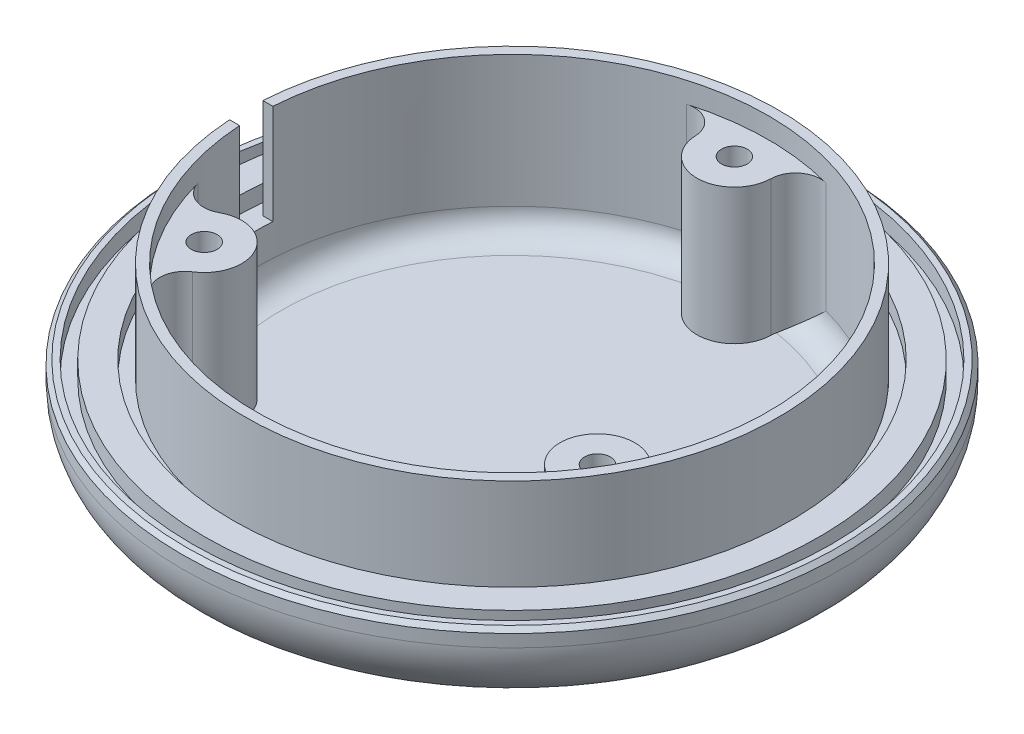
SolidWorks part; units mm, degrees
ref_plane "Plan de face" through (0, 0, 0) normal (0, 0, 1) x (1, 0, 0)
ref_plane "Plan de dessus" through (0, 0, 0) normal (0, 1, 0) x (1, 0, 0)
ref_plane "Plan de droite" through (0, 0, 0) normal (1, 0, 0) x (0, 0, -1)
sketch "Esquisse2" plane through (0, 0, 0) normal (0, 0, 1) x (1, 0, 0)
  line L0 (-39.6, 8) -> (-39.6, 10)
  line L1 (0, 0) -> (-32, 0)
  line L2 (-39.6, 10) -> (-38.4, 10)
  line L3 (-38.4, 10) -> (-38.4, 8)
  line L4 (0, 24.4124) -> (0, -18.1737) construction
  line L5 (0, 1.2) -> (-30.8, 1.2)
  line L7 (-32, 8) -> (-32, 20)
  line L8 (-32, 20) -> (-30.8, 20)
  line L9 (-30.8, 20) -> (-30.8, 1.2)
  line L10 (-32, 8) -> (-33.5, 8)
  line L11 (0, 0) -> (0, 1.2)
  line L12 (-38.4, 8) -> (-36.9, 8)
  line L13 (-36.9, 8) -> (-36.9, 10)
  line L17 (-36.9, 10) -> (-33.5, 10)
  line L18 (-33.5, 8) -> (-33.5, 10)
  arc A0 (-39.6, 8) -> (-32, 0) centre (-31.5895, 8) ccw
  circle A1 centre (-34.3, 4.5) radius 2.75
  point P12 (-39.6, 10)
  dimension "D2" = 32
  dimension "D5" = 12
  dimension "D20" = 5.5
  dimension "D4" = 1.5
  dimension "D6" = 30.8
  dimension "D7" = 2
  dimension "D8" = 3.4
  dimension "D9" = 90
  dimension "D10" = 2
  dimension "D11" = 1.2
  dimension "D12" = 2
  dimension "D13" = 1.2
  dimension "D14" = 8
  dimension "D17" = 1.5
  dimension "D18" = 1.2
  dimension "D19" = 8
  dimension "D21" = 3.5
  dimension "D22" = 4.5
revolve "Révolution1" add sketch "Esquisse2" angle 360 about L4
sketch "Esquisse3" plane through (0, 0, 0) normal (1, 0, 0) x (0, 0, -1)
  line L0 (-39.6, 8) -> (39.6, 8) construction
  line L1 (2, 21.9768) -> (-2, 21.9768)
  line L2 (2, 21.9768) -> (2, 8)
  line L3 (2, 8) -> (-2, 8)
  line L4 (-2, 21.9768) -> (-2, 8)
  dimension "D1" = 2
  dimension "D2" = 4
extrude "Enlèv. mat.-Extru.1" cut sketch "Esquisse3" against normal blind 32
sketch "Esquisse4" plane through (0, 1.2, 0) normal (0, 1, 0) x (1, 0, 0)
  line L0 (4.2215, 26.9986) -> (4.2215, 30.6492)
  line L1 (-4.7785, 26.9986) -> (-4.7785, 30.5673)
  line L2 (21.2707, -17.1552) -> (24.4323, -18.9805)
  line L3 (25.7707, -9.361) -> (28.8614, -11.1454)
  line L4 (-25.4922, -9.8434) -> (-28.6538, -11.6687)
  line L5 (-20.9922, -17.6376) -> (-24.0828, -19.422)
  arc A0 (4.2215, 30.6492) -> (-4.7785, 30.5673) centre (0, 0) ccw
  circle A1 centre (-0.2785, 26.9986) radius 1.55
  arc A2 (24.4323, -18.9805) -> (28.8614, -11.1454) centre (0, 0) ccw
  arc A3 (-4.7785, 26.9986) -> (4.2215, 26.9986) centre (-0.2785, 26.9986) ccw
  circle A4 centre (23.5207, -13.2581) radius 1.55
  arc A5 (25.7707, -9.361) -> (21.2707, -17.1552) centre (23.5207, -13.2581) ccw
  arc A6 (-28.6538, -11.6687) -> (-24.0828, -19.422) centre (0, 0) ccw
  circle A7 centre (-23.2422, -13.7405) radius 1.55
  arc A8 (-20.9922, -17.6376) -> (-25.4922, -9.8434) centre (-23.2422, -13.7405) ccw
  circle A13 centre (23.5207, -13.2581) radius 1.55 [skipped]
  circle A14 centre (-23.2422, -13.7405) radius 1.55 [skipped]
  point P8 (0, 0)
  point P9 (0, 0)
  point P10 (0, 0)
  point P11 (0, 0)
  point P12 (0, 0)
  point P13 (0, 0)
  point P16 (0, 0)
  point P21 (0, 0)
  point P33 (0, 0)
  point P34 (0, 0)
  point P35 (0, 0)
  point P37 (0, 0)
  point P41 (0, 0)
  dimension "D1" = 3.1
  dimension "D3" = 3
  dimension "D4" = 3
  dimension "D5" = 4.5
  dimension "D2" = 27
extrude "Boss.-Extru.1" add sketch "Esquisse4" along normal blind 16.3
fillet "Congé1" radius 3 9 edges at (0.2815, 1.2, 30.7987) (26.5317, 1.2, -15.6432) (-26.8132, 1.2, -15.1555) (-28.5326, 9.35, 11.5988) (28.7399, 9.35, 11.0752) (24.3111, 9.35, 18.9106) (-4.7785, 9.35, -30.4271) (4.2215, 9.35, -30.5093) (-23.9613, 9.35, 19.3518)
chamfer "Chanfrein1" distance 0.5 angle 45 1 edges at (0, 10, 39.6)
